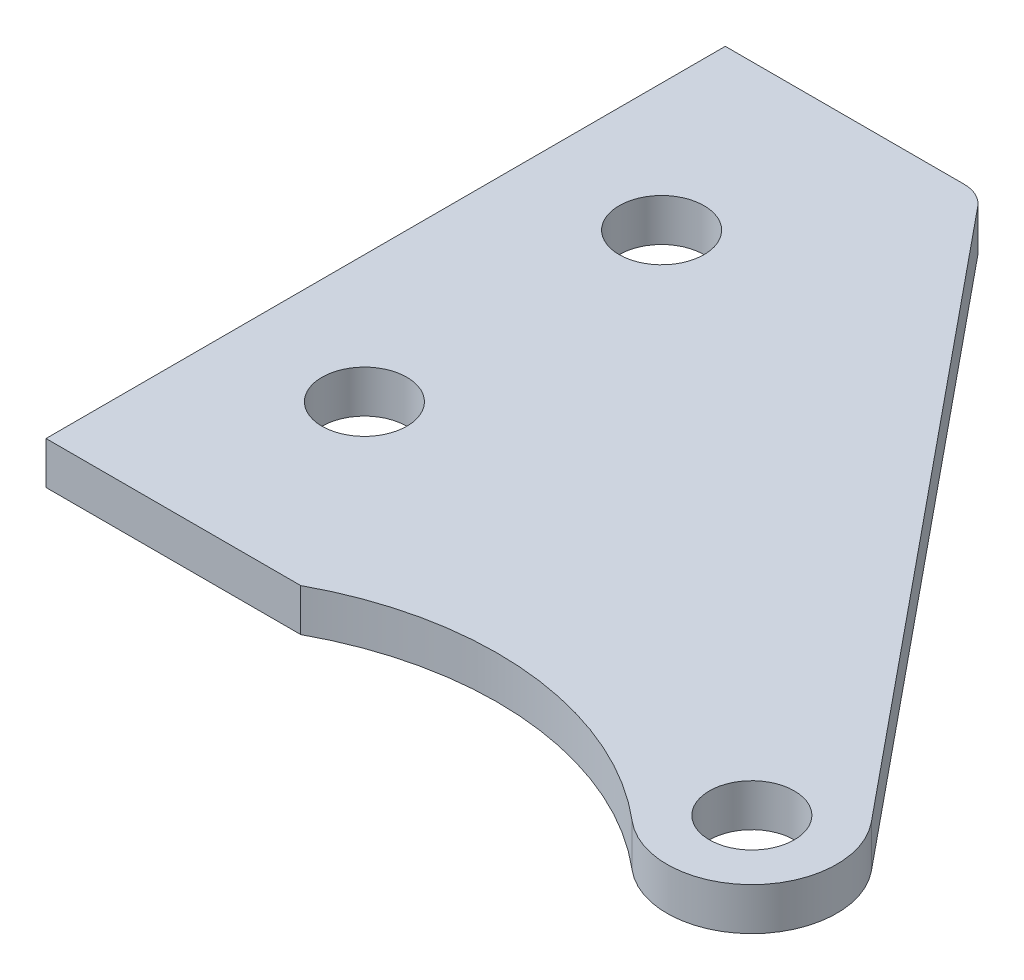
SolidWorks part; units mm, degrees
material "6061-T6 (SS)"
ref_plane "Front" through (0, 0, 0) normal (0, 0, 1) x (1, 0, 0)
ref_plane "Top" through (0, 0, 0) normal (0, 1, 0) x (1, 0, 0)
ref_plane "Right" through (0, 0, 0) normal (1, 0, 0) x (0, 0, -1)
sketch "Sketch1" plane through (0, 0, 0) normal (0, 1, 0) x (1, 0, 0)
  line L1 (0, 50.8) -> (19.05, 50.8)
  line L3 (19.05, 50.8) -> (55.7137, 6.0089)
  line L4 (0, 50.8) -> (0, 0)
  line L6 (0, 0) -> (19.05, 0)
  arc A0 (55.7137, 6.0089) -> (46.6945, -2.8575) centre (50.8, 1.9868) cw
  arc A3 (19.05, 0) -> (46.6945, -2.8575) centre (30.784, -21.6311) cw
  dimension "D1" = 19.05
  dimension "D3" = 6.35
  dimension "D4" = 50.8
  dimension "D5" = 50.8
extrude "Boss-Extrude1" add sketch "Sketch1" along normal blind 3.175
hole_wizard "1/4 (0.25) Diameter Hole2" positions "Sketch4" profile "Sketch3" hole size "1/4" standard "ANSI Inch" end condition through all
sketch "Sketch4" plane through (0, 0, 0) normal (0, -1, 0) x (-1, 0, 0)
  point P0 (-50.8, 1.9868)
sketch "Sketch3" plane through (50.8, 0, -1.9868) normal (1, 0, 0) x (0, 0, -1)
  line L0 (0, 0) -> (0, 3.175)
  line L1 (0, 3.175) -> (3.175, 3.175)
  line L2 (3.175, 3.175) -> (3.175, 0)
  line L5 (3.175, 0) -> (0, 0)
  line L11 (0, -6.35) -> (0, 107.95) construction
  dimension "Thru Hole Dia." = 6.35
  dimension "Thru Hole Depth" = 3.175
hole_wizard "1/4 (0.25) Diameter Hole1" positions "Sketch7" profile "Sketch8" hole size "1/4" standard "ANSI Inch" end condition through all
sketch "Sketch7" plane through (0, 3.175, 0) normal (0, 1, 0) x (1, 0, 0)
  line L9 (9.525, 0) -> (9.525, 14.2875) construction
  line L10 (0, 0) -> (19.05, 0) construction
  line L11 (9.525, 14.2875) -> (9.525, 36.5125) construction
  line L12 (9.525, 36.5125) -> (9.525, 50.8) construction
  line L13 (19.05, 50.8) -> (0, 50.8) construction
  point P0 (9.525, 36.5125)
  point P2 (9.525, 14.2875)
  dimension "D1" = 22.225
sketch "Sketch8" plane through (9.525, 3.175, -36.5125) normal (1, 0, 0) x (0, 0, 1)
  line L0 (0, 0) -> (0, 3.175)
  line L1 (0, 3.175) -> (3.175, 3.175)
  line L2 (3.175, 3.175) -> (3.175, 0)
  line L5 (3.175, 0) -> (0, 0)
  line L11 (0, -6.35) -> (0, 107.95) construction
  dimension "Thru Hole Dia." = 6.35
  dimension "Thru Hole Depth" = 3.175
fillet "Fillet1" radius 2.54 1 edges at (19.05, 1.5875, -50.8)
